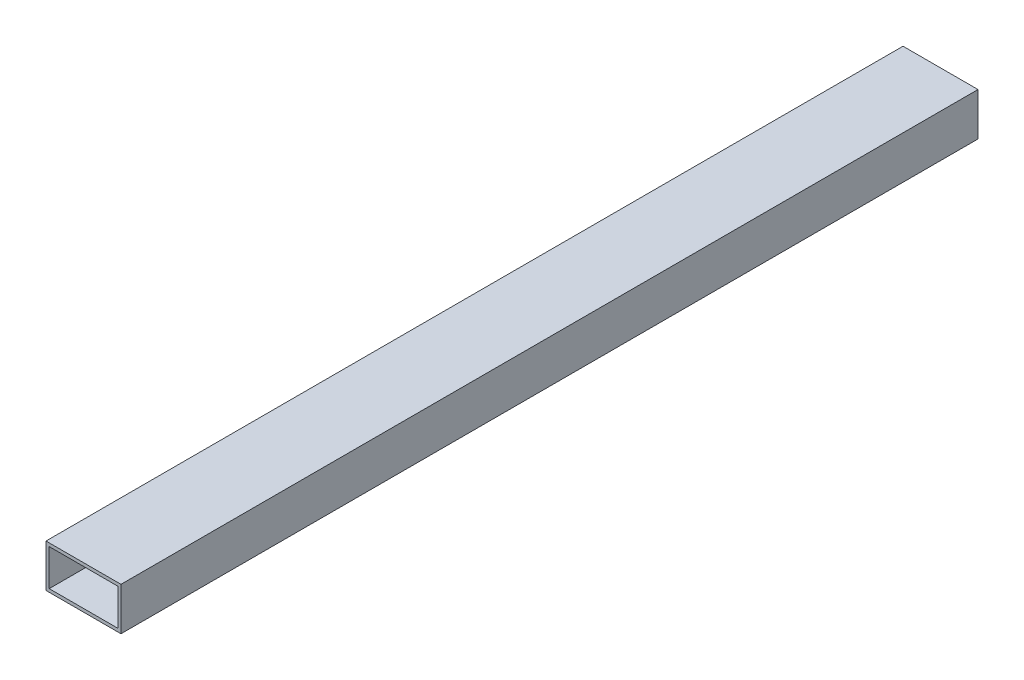
SolidWorks part; units mm, degrees
material "AISI 1020 Acier laminé à froid"
ref_plane "Plan de face" through (0, 0, 0) normal (0, 0, 1) x (1, 0, 0)
ref_plane "Plan de dessus" through (0, 0, 0) normal (0, 1, 0) x (1, 0, 0)
ref_plane "Plan de droite" through (0, 0, 0) normal (1, 0, 0) x (0, 0, -1)
sketch "Esquisse1" plane through (0, 0, 0) normal (0, 0, 1) x (1, 0, 0)
  line L1 (0, 0) -> (35, 0)
  line L2 (0, 0) -> (0, 20)
  line L3 (0, 20) -> (35, 20)
  line L4 (35, 0) -> (35, 20)
  line L5 (1.5, 18.5) -> (33.5, 18.5)
  line L6 (1.5, 18.5) -> (1.5, 1.5)
  line L7 (1.5, 1.5) -> (33.5, 1.5)
  line L8 (33.5, 18.5) -> (33.5, 1.5)
  dimension "D1" = 35
  dimension "D2" = 20
  dimension "D3" = 1.5
  dimension "D4" = 1.5
  dimension "D5" = 1.5
  dimension "D6" = 1.5
extrude "Boss.-Extru.1" add sketch "Esquisse1" along normal blind 400
sketch "Esquisse2" plane through (0, 0, 0) normal (0, 1, 0) x (1, 0, 0)
  line L0 (0, -400) -> (35, -365)
  line L1 (35, -400) -> (35, 0) construction
  line L2 (0, -400) -> (35, -400)
  line L3 (35, -400) -> (35, -365)
  dimension "D1" = 45
extrude "Enlèv. mat.-Extru.1" [suppressed] cut sketch "Esquisse2" along normal through all
sketch "Esquisse4" plane through (0, 0, 0) normal (0, 1, 0) x (1, 0, 0)
  line L0 (0, 0) -> (35, -35)
  line L1 (35, -400) -> (35, 0) construction
  line L2 (35, -35) -> (35, 0)
  line L3 (35, 0) -> (0, 0)
  dimension "D1" = 45
extrude "Enlèv. mat.-Extru.3" [suppressed] cut sketch "Esquisse4" along normal through all
